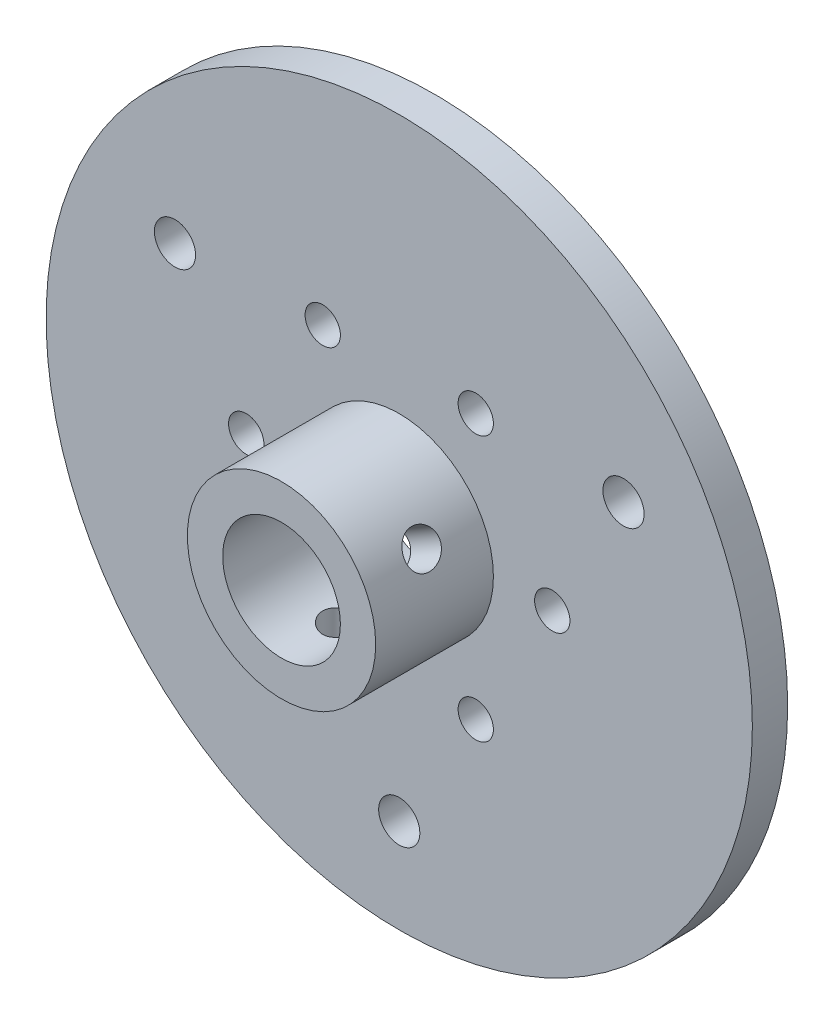
SolidWorks part; units mm, degrees
material "1060 Alloy"
ref_plane "Front Plane" through (0, 0, 0) normal (0, 0, 1) x (1, 0, 0)
ref_plane "Top Plane" through (0, 0, 0) normal (0, 1, 0) x (1, 0, 0)
ref_plane "Right Plane" through (0, 0, 0) normal (1, 0, 0) x (0, 0, -1)
sketch "Sketch2" plane through (0, 0, 0) normal (0, 0, 1) x (1, 0, 0)
  circle A0 centre (0, 0) radius 5
  circle A2 centre (0, 0) radius 22 construction
  circle A3 centre (0, 0) radius 30
  circle A4 centre (0, -22) radius 1.75
  circle A5 centre (-19.0526, 11) radius 1.75
  circle A6 centre (19.0526, 11) radius 1.75
  point P13 (0, 0)
  dimension "D1" = 3
  dimension "D2" = 44
  dimension "D3" = 3.5
  dimension "D4" = 10
  dimension "D5" = 60
extrude "Boss-Extrude1" add sketch "Sketch2" along normal blind 3
sketch "Sketch3" plane through (0, 0, 3) normal (0, 0, 1) x (1, 0, 0)
  circle A0 centre (0, 0) radius 8
  circle A1 centre (0, 0) radius 5
  dimension "D1" = 16
extrude "Boss-Extrude2" add sketch "Sketch3" along normal blind 10
sketch "Sketch4" plane through (0, 0, 3) normal (0, 0, 1) x (1, 0, 0)
  line L0 (0, 0) -> (-17.8949, 30.9948) construction
  line L1 (0, 0) -> (0, 33.1815) construction
  line L2 (0, 0) -> (16.5859, 28.7276) construction
  circle A9 centre (0, 0) radius 13
  circle A10 centre (-6.5, 11.2583) radius 1.5
  circle A11 centre (13, 0) radius 1.5
  circle A12 centre (-6.5, -11.2583) radius 1.5
  circle A14 centre (6.5, 11.2583) radius 1.5
  circle A15 centre (6.5, -11.2583) radius 1.5
  circle A16 centre (-13, 0) radius 1.5
  point P11 (0, 0)
  point P12 (0, 0)
  point P13 (0, 0)
  point P24 (0, 0)
  dimension "D1" = 3
  dimension "D2" = 3
  dimension "D4" = 26
  dimension "D3" = 30
  dimension "D5" = 2
  dimension "D6" = 30
extrude "Cut-Extrude2" cut sketch "Sketch4" against normal through all contours A12 | A11 | A10 | A16 | A14 | A15
sketch "Sketch12" plane through (0, 0, 0) normal (0, 1, 0) x (1, 0, 0)
  circle A0 centre (0, -8) radius 1.5
  dimension "D1" = 3
  dimension "D2" = 8
extrude "Cut-Extrude3" cut sketch "Sketch12" against normal blind 11.4938
pattern_circular "CirPattern1" count 3 every 120 about axis through (0, 0, 13) along (0, 0, 1) of "Cut-Extrude3"
